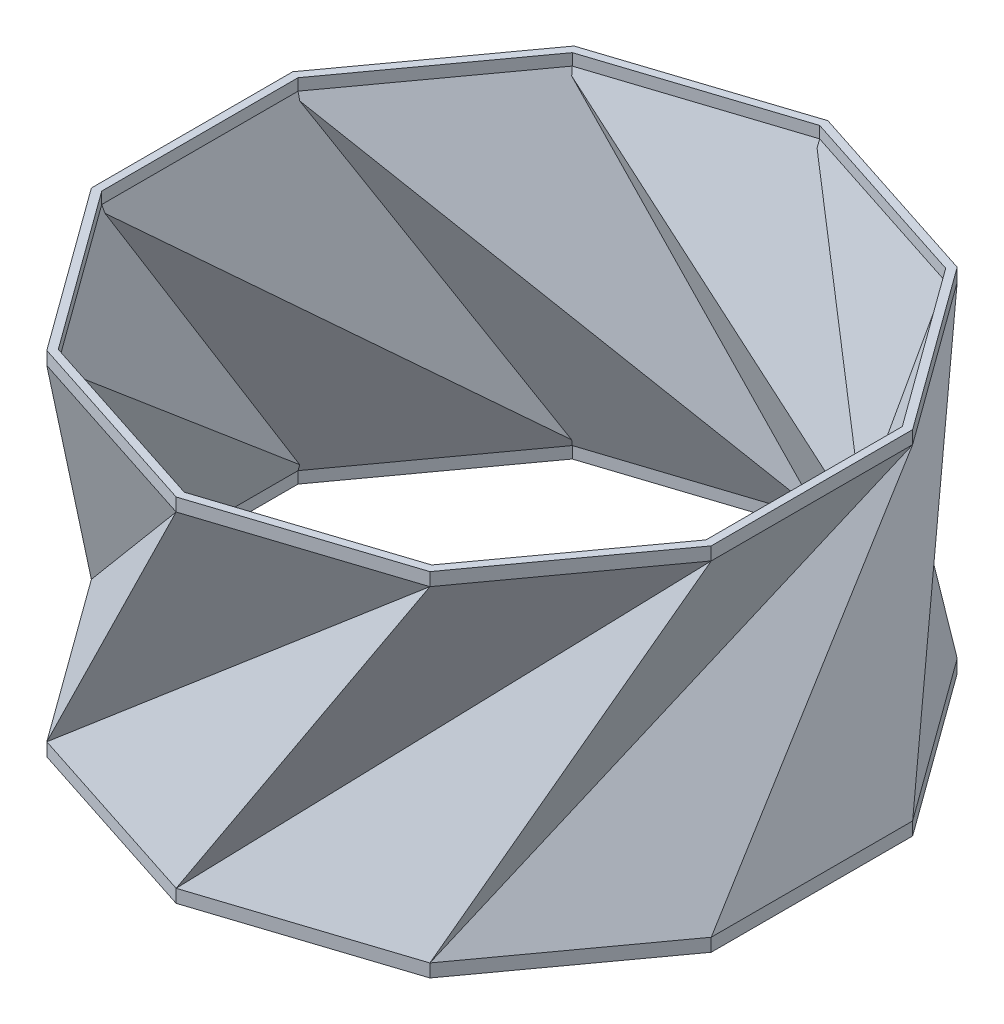
SolidWorks part; units mm, degrees
ref_plane "정면" through (0, 0, 0) normal (0, 0, 1) x (1, 0, 0)
ref_plane "윗면" through (0, 0, 0) normal (0, 1, 0) x (1, 0, 0)
ref_plane "우측면" through (0, 0, 0) normal (1, 0, 0) x (0, 0, -1)
sketch "스케치1" plane through (0, 0, 0) normal (0, 1, 0) x (1, 0, 0)
  line L0 (0, -55) -> (0, 55) construction
  line L1 (14.6946, -20.2254) -> (23.7764, -7.7254)
  line L2 (23.7764, -7.7254) -> (23.7764, 7.7254)
  line L3 (23.7764, 7.7254) -> (14.6946, 20.2254)
  line L4 (14.6946, 20.2254) -> (0, 25)
  line L5 (0, 25) -> (-14.6946, 20.2254)
  line L6 (-14.6946, 20.2254) -> (-23.7764, 7.7254)
  line L7 (-23.7764, 7.7254) -> (-23.7764, -7.7254)
  line L8 (-23.7764, -7.7254) -> (-14.6946, -20.2254)
  line L9 (-14.6946, -20.2254) -> (0, -25)
  line L10 (0, -25) -> (14.6946, -20.2254)
  circle A0 centre (0, 0) radius 25 construction
  dimension "D1" = 50
extrude "보스-돌출1" add sketch "스케치1" along normal blind 25
ref_plane "평면1" through (-16.993, 7.6303, 12.3462) normal (-0.7604, 0.3414, 0.5525) x (0.504, -0.2263, 0.8335)
sketch "스케치2" plane through (-16.993, 7.6303, 12.3462) normal (-0.7604, 0.3414, 0.5525) x (0.504, -0.2263, 0.8335)
  line L0 (-5.5435, -9.7395) -> (15.1809, 22.8063)
  line L1 (15.1809, 22.8063) -> (9.4528, -6.0193)
sketch "스케치3" plane through (-19.2355, 0, 13.9754) normal (-0.809, 0, 0.5878) x (0.5878, 0, 0.809)
  line L0 (-7.7254, 0) -> (7.7254, 25)
ref_plane "평면2" through (-23.7764, 0, 7.7254) normal (0.6162, 0.6479, 0.4477) x (0.7876, -0.507, -0.3503)
sketch "스케치4" plane through (-23.7764, 0, 7.7254) normal (0.6162, 0.6479, 0.4477) x (0.7876, -0.507, -0.3503)
  line L0 (0, 0) -> (2.7737, -10.2838) construction
  line L1 (0, 0) -> (-9.9005, 3.9281) construction
  line L2 (0, 0) -> (2.7737, -10.2838)
  line L3 (0, 0) -> (-9.9005, 3.9281)
  line L4 (-9.9005, 3.9281) -> (2.7737, -10.2838)
extrude "컷-돌출1" cut sketch "스케치4" along normal up to vertex (38.584 mm away) up to point (0, 25, 25)
pattern_circular "원형 패턴1" count 10 over 360 about axis through (0, 25, 0) along (0, 1, 0) of "컷-돌출1"
sketch "스케치6" plane through (0, 25, 0) normal (0, 1, 0) x (1, 0, 0)
  line L10 (0, -25) -> (14.6946, -20.2254)
  line L11 (14.6946, -20.2254) -> (23.7764, -7.7254)
  line L12 (23.7764, -7.7254) -> (23.7764, 7.7254)
  line L13 (23.7764, 7.7254) -> (14.6946, 20.2254)
  line L14 (14.6946, 20.2254) -> (0, 25)
  line L15 (0, 25) -> (-14.6946, 20.2254)
  line L16 (-14.6946, 20.2254) -> (-23.7764, 7.7254)
  line L17 (-23.7764, 7.7254) -> (-23.7764, -7.7254)
  line L18 (-23.7764, -7.7254) -> (-14.6946, -20.2254)
  line L19 (-14.6946, -20.2254) -> (0, -25)
  line L20 (0, -25) -> (14.6946, -20.2254)
  line L21 (14.6946, -20.2254) -> (23.7764, -7.7254)
  line L22 (23.7764, -7.7254) -> (23.7764, 7.7254)
  line L23 (23.7764, 7.7254) -> (14.6946, 20.2254)
  line L24 (14.6946, 20.2254) -> (0, 25)
  line L25 (0, 25) -> (-14.6946, 20.2254)
  line L26 (-14.6946, 20.2254) -> (-23.7764, 7.7254)
  line L27 (-23.7764, 7.7254) -> (-23.7764, -7.7254)
  line L28 (-23.7764, -7.7254) -> (-14.6946, -20.2254)
  line L29 (-14.6946, -20.2254) -> (0, -25)
  dimension "D1" = 0
extrude "보스-돌출2" add sketch "스케치6" along normal blind 1
sketch "스케치7" plane through (0, 0, 0) normal (0, -1, 0) x (1, 0, 0)
  line L10 (14.6946, 20.2254) -> (0, 25)
  line L11 (0, 25) -> (-14.6946, 20.2254)
  line L12 (-14.6946, 20.2254) -> (-23.7764, 7.7254)
  line L13 (-23.7764, 7.7254) -> (-23.7764, -7.7254)
  line L14 (-23.7764, -7.7254) -> (-14.6946, -20.2254)
  line L15 (-14.6946, -20.2254) -> (0, -25)
  line L16 (0, -25) -> (14.6946, -20.2254)
  line L17 (14.6946, -20.2254) -> (23.7764, -7.7254)
  line L18 (23.7764, -7.7254) -> (23.7764, 7.7254)
  line L19 (23.7764, 7.7254) -> (14.6946, 20.2254)
  line L20 (14.6946, 20.2254) -> (0, 25)
  line L21 (0, 25) -> (-14.6946, 20.2254)
  line L22 (-14.6946, 20.2254) -> (-23.7764, 7.7254)
  line L23 (-23.7764, 7.7254) -> (-23.7764, -7.7254)
  line L24 (-23.7764, -7.7254) -> (-14.6946, -20.2254)
  line L25 (-14.6946, -20.2254) -> (0, -25)
  line L26 (0, -25) -> (14.6946, -20.2254)
  line L27 (14.6946, -20.2254) -> (23.7764, -7.7254)
  line L28 (23.7764, -7.7254) -> (23.7764, 7.7254)
  line L29 (23.7764, 7.7254) -> (14.6946, 20.2254)
  dimension "D1" = 0
extrude "보스-돌출3" add sketch "스케치7" along normal blind 1
shell "쉘1" thickness 0.6 removed face at (0, -1, 0) removed face at (0, 26, 0)
